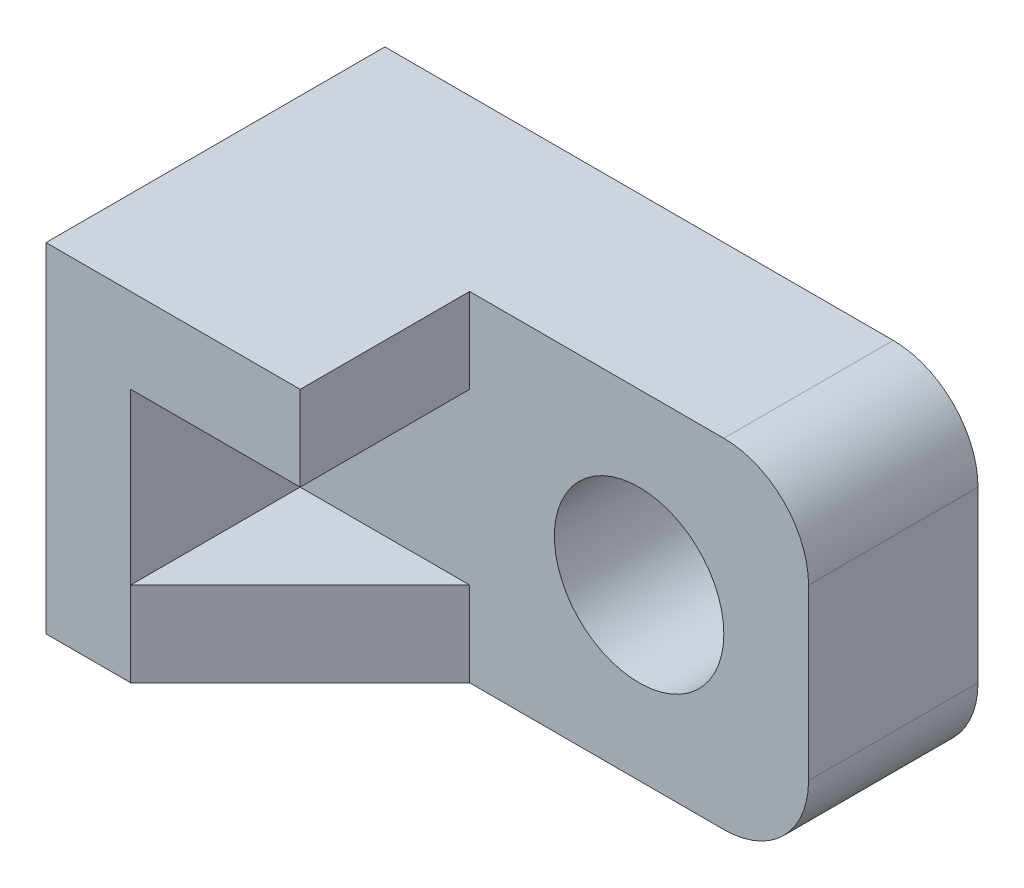
SolidWorks part; units mm, degrees
ref_plane "Front Plane" through (0, 0, 0) normal (0, 0, 1) x (1, 0, 0)
ref_plane "Top Plane" through (0, 0, 0) normal (0, 1, 0) x (1, 0, 0)
ref_plane "Right Plane" through (0, 0, 0) normal (1, 0, 0) x (0, 0, -1)
sketch "Sketch2" plane through (0, 0, 0) normal (0, 0, 1) x (1, 0, 0)
  line L0 (40, 10) -> (30, 10) construction
  line L1 (-30, 20) -> (30, 20)
  line L2 (-30, 20) -> (-30, -20)
  line L3 (-30, -20) -> (30, -20)
  line L4 (30, 20) -> (30, -20)
  line L5 (-30, 20) -> (30, -20) construction
  line L6 (-30, -20) -> (30, 20) construction
  line L7 (-20, 20) -> (-20, -20)
  line L8 (-20, 10) -> (0, 10)
  line L9 (0, 10) -> (0, 20)
  line L10 (-20, -10) -> (0, -10)
  line L11 (0, -10) -> (0, -20)
  line L14 (30, 20) -> (30, 0) construction
  line L15 (40, -10) -> (40, 10)
  circle A2 centre (20, 0) radius 10
  arc A3 (40, 10) -> (30, 20) centre (30, 10) ccw
  arc A4 (40, -10) -> (30, -20) centre (30, -10) cw
  point P0 (0, 0)
  point P7 (0, 0)
  dimension "D1" = 10
  dimension "D2" = 10
  dimension "D5" = 20
  dimension "D8" = 20
  dimension "D10" = 20
  dimension "D11" = 10
  dimension "D13" = 50
  dimension "D3" = 40
  dimension "D4" = 10
  dimension "D6" = 20
  dimension "D7" = 10
  dimension "D9" = 70
  dimension "D12" = 10
  dimension "D14" = 20
other "AlignGroup1"
extrude "Boss-Extrude8" add sketch "Sketch2" along normal blind 20 contours L11 L10 L7 L3 | L8 L9 L1 L7 | L7 L1 L2 L3 region at (-25, 0, 0) region at (-10, 15, 0) region at (-10, -15, 0)
extrude "Boss-Extrude9" add sketch "Sketch2<10>" against normal blind 20 contours L11 L10 L7 L3 | L7 L1 L2 L3 | L8 L9 L1 L7 | L4 A2 L1 L9 L8 L7 L10 L11 L3 | A4 L15 A3 L4 region at (-25, 0, 0) region at (-10, 15, 0) region at (6.0014, 0, 0) region at (-10, -15, 0) region at (34.6675, 0, 0)
sketch "Sketch2<10>" plane through (0, 0, 0) normal (0, 0, 1) x (1, 0, 0) same geometry as "Sketch2"
chamfer "Chamfer1" distance 20 angle 45 1 edges at (0, -15, 20)
